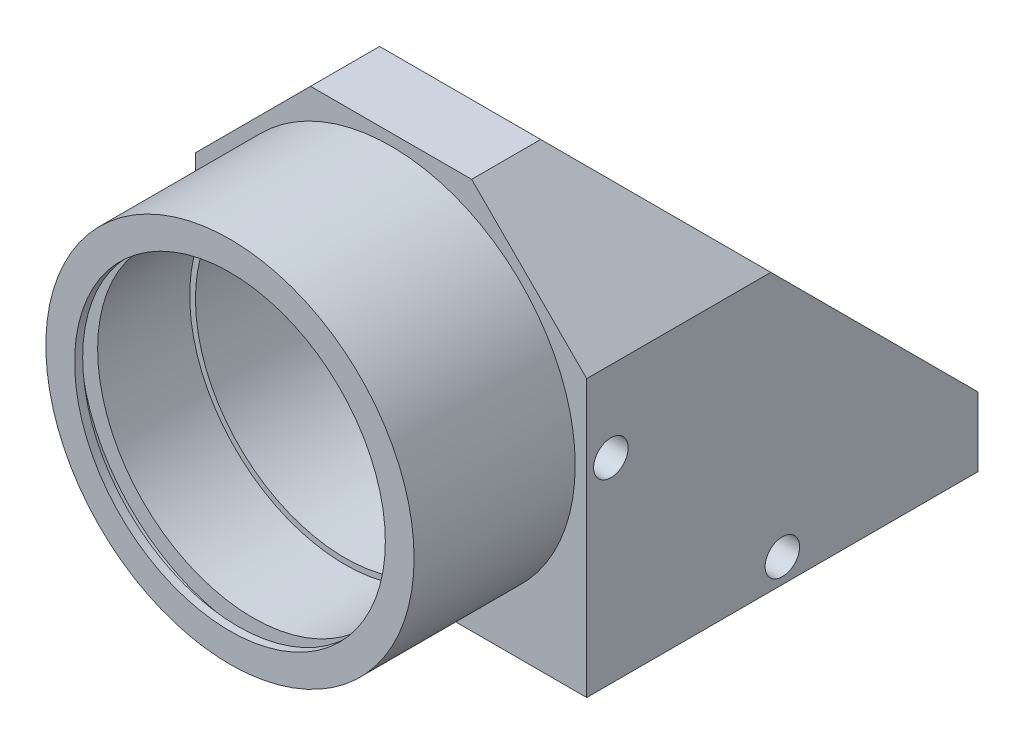
SolidWorks part; units mm, degrees
material "1060 合金"
ref_plane "前视基准面" through (0, 0, 0) normal (0, 0, 1) x (1, 0, 0)
ref_plane "上视基准面" through (0, 0, 0) normal (0, 1, 0) x (1, 0, 0)
ref_plane "右视基准面" through (0, 0, 0) normal (1, 0, 0) x (0, 0, -1)
sketch "草图1" plane through (0, 0, 0) normal (0, 0, 1) x (1, 0, 0)
  line L0 (0, 0) -> (0, 67.9685) construction
  line L1 (0, 0) -> (83.4241, 0) construction
  line L3 (-17, -17) -> (17, -17)
  line L4 (-17, -17) -> (-17, 17)
  line L5 (-17, 17) -> (17, 17)
  line L6 (17, -17) -> (17, 17)
  line L7 (-17, -17) -> (17, 17) construction
  line L8 (-17, 17) -> (17, -17) construction
  circle A0 centre (0, 0) radius 13
  dimension "D1" = 26
  dimension "D2" = 34
  dimension "D3" = 34
extrude "凸台-拉伸1" add sketch "草图1" along normal blind 48
sketch "草图2" plane through (0, 0, 48) normal (0, 0, 1) x (1, 0, 0)
  circle A0 centre (0, 0) radius 13.5
  dimension "D1" = 27
extrude "切除-拉伸1" cut sketch "草图2" against normal blind 10
sketch "草图3" plane through (0, -17, 0) normal (0, -1, 0) x (1, 0, 0)
  line L0 (0, 0) -> (0, 57.5158) construction
  line L1 (-17, 48) -> (17, 48) construction
  circle A0 centre (0, 17) radius 13
  dimension "D1" = 26
  dimension "D2" = 31
extrude "切除-拉伸2" cut sketch "草图3" against normal blind 10
chamfer "倒角1" distance 10 angle 45 2 edges at (17, 17, 24) (-17, 17, 24)
chamfer "倒角2" distance 28 angle 45 1 edges at (0, 17, 0)
sketch "草图5" plane through (0, 0, 48) normal (0, 0, 1) x (1, 0, 0)
  line L0 (-7, 17) -> (-17, 7)
  line L1 (-17, 7) -> (-17, -17)
  line L2 (-17, -17) -> (17, -17)
  line L3 (17, -17) -> (17, 17)
  line L4 (17, -17) -> (17, 7) construction
  line L5 (17, 17) -> (-7, 17)
  circle A0 centre (0, 0) radius 16
  circle A1 centre (0, 0) radius 13.5 construction
  dimension "D1" = 2.5
extrude "切除-拉伸4" cut sketch "草图5" against normal blind 14
hole_wizard "M4 螺纹孔1" positions "草图7" profile "草图6" tap size "M4" standard "GB"
sketch "草图7" plane through (0, -17, 0) normal (0, -1, 0) x (1, 0, 0)
  line L0 (0, 17) -> (21.032, 38.032) construction
  line L2 (17, 34) -> (17, 0) construction
  line L3 (0, 17) -> (26.7129, 17) construction
  point P0 (13, 30)
  point P14 (13, 4)
  point P15 (-13, 4)
  point P16 (-13, 30)
  dimension "D1" = 4
  dimension "D3" = 45
  dimension "D2" = 4
sketch "草图6" plane through (13, -17, 30) normal (1, 0, 0) x (0, 0, -1)
  line L0 (0, 0) -> (0, 8.9914)
  line L1 (0, 8.9914) -> (1.65, 8)
  line L2 (1.65, 8) -> (1.65, 0)
  line L5 (1.65, 0) -> (0, 0)
  line L10 (0, 8.9914) -> (-1.65, 8) construction
  line L11 (0, -6.35) -> (0, 107.95) construction
  dimension "螺纹孔钻头直径" = 3.3
  dimension "螺纹孔钻头深度" = 8
  dimension "导头角度" = 118
cosmetic thread "孔螺蚊线1" parameters "D1"=8, "D2"=4
cosmetic thread "孔螺蚊线2" parameters "D1"=8, "D2"=4
cosmetic thread "孔螺蚊线3" parameters "D1"=8, "D2"=4
cosmetic thread "孔螺蚊线4" parameters "D1"=8, "D2"=4
sketch "草图8" plane through (0, 0, 0) normal (1, 0, 0) x (0, 0, -1)
  line L0 (0, 0) -> (-57.5114, 0) construction
  line L1 (-38, 13.5) -> (-48, 13.5) construction
  line L2 (-46, 13.5) -> (-47.3, 13.5)
  line L3 (-46, 13.5) -> (-46, 15)
  line L4 (-46, 15) -> (-47.3, 15)
  line L5 (-47.3, 13.5) -> (-47.3, 15)
  line L6 (-48, 16) -> (-48, -16) construction
  dimension "D1" = 1.3
  dimension "D2" = 2
  dimension "D3" = 15
revolve "切除-旋转1" cut sketch "草图8" angle 360 about L0
sketch "草图9" plane through (0, 0, 34) normal (0, 0, 1) x (1, 0, 0)
  line L0 (0, 0) -> (30.6315, 0) construction
  line L1 (17, -17) -> (17, 7) construction
  line L2 (25, 7) -> (17, 7)
  line L3 (25, 7) -> (25, -7)
  line L4 (25, -7) -> (17, -7)
  line L5 (17, 7) -> (17, -7)
  line L6 (25, 7) -> (17, -7) construction
  line L7 (25, -7) -> (17, 7) construction
  line L8 (21, 9.6972) -> (21, -9.1795) construction
  point P3 (21, 0)
  dimension "D1" = 14
  dimension "D2" = 8
extrude "凸台-拉伸2" [suppressed] add sketch "草图9" against normal blind 7
sketch "草图10" plane through (0, 0, 0) normal (1, 0, 0) x (0, 0, -1)
  line L0 (-34, -17) -> (-34, 7) construction
  line L1 (-34, -17) -> (0, -17) construction
  circle A0 centre (-31.9, 0) radius 1.5
  circle A1 centre (-17, -14.9) radius 1.5
  dimension "D1" = 3
  dimension "D2" = 3
  dimension "D3" = 2.1
  dimension "D4" = 17
  dimension "D5" = 2.1
  dimension "D6" = 17
extrude "切除-拉伸5" cut sketch "草图10" along normal up to next
sketch "草图11" plane through (0, 0, 34) normal (0, 0, 1) x (1, 0, 0)
  line L0 (0, 32.5) -> (0, 17)
  line L1 (6.6579, -17) -> (27.6993, -17)
  line L2 (7, 17) -> (-7, 17) construction
  line L11 (17, -17) -> (17, 7)
  line L12 (-7, 17) -> (-17, 7)
  line L13 (7, 17) -> (-7, 17)
  line L15 (-17, 7) -> (-17, -17)
  line L16 (-17, -17) -> (17, -17)
  line L20 (17, -17) -> (17, 7)
  line L21 (17, 7) -> (7, 17)
  line L22 (7, 17) -> (0, 17)
  line L23 (17, 7) -> (7, 17)
  arc A0 (27.6993, -17) -> (0, 32.5) centre (0, 0) ccw
  dimension "D2" = 65
  dimension "D1" = 0
extrude "凸台-拉伸3" [suppressed] add sketch "草图11" against normal blind 4
move or copy body "实体-移动/复制1" [suppressed] bodies to move or copy 107
